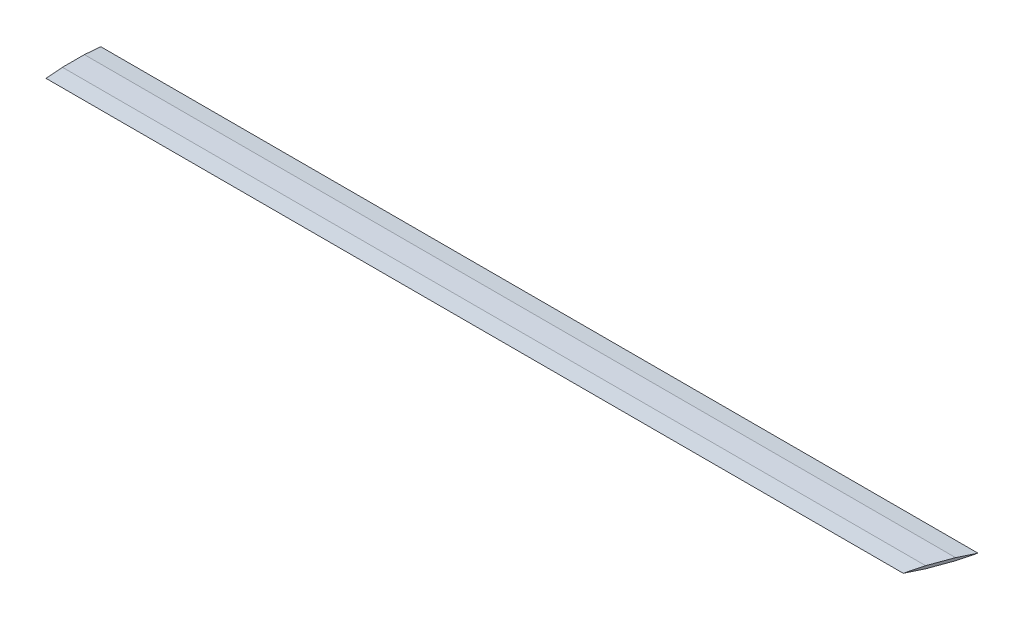
SolidWorks part; units mm, degrees
material "Balsa"
ref_plane "Front Plane" through (0, 0, 0) normal (0, 0, 1) x (1, 0, 0)
ref_plane "Top Plane" through (0, 0, 0) normal (0, 1, 0) x (1, 0, 0)
ref_plane "Right Plane" through (0, 0, 0) normal (1, 0, 0) x (0, 0, -1)
sketch "Sketch1" plane through (0, 0, 0) normal (0, 1, 0) x (1, 0, 0)
  line L0 (0, 0) -> (320, 0)
  line L1 (320, 0) -> (312.7206, -20)
  line L2 (312.7206, -20) -> (0, -20)
  line L3 (0, -20) -> (0, 0)
  dimension "D1" = 20
  dimension "D2" = 320
  dimension "D4" = 110
  dimension "D5" = 20
extrude "Boss-Extrude1" add sketch "Sketch1" along normal blind 1 contours L3 L2 L1 L0 region at (158.1871, 0, 9.9617)
chamfer "Chamfer1" distance 6 distance2 0.5 2 edges at (160, 0, 0) (160, 1, 0) first distance on face at (158.1801, 0, 10) first distance on face at (158.1801, 1, 10)
chamfer "Chamfer2" distance 6 distance2 0.5 2 edges at (156.3603, 0, 20) (156.3603, 1, 20) first distance on face at (157.6342, 0, 13) first distance on face at (157.6342, 1, 13)
